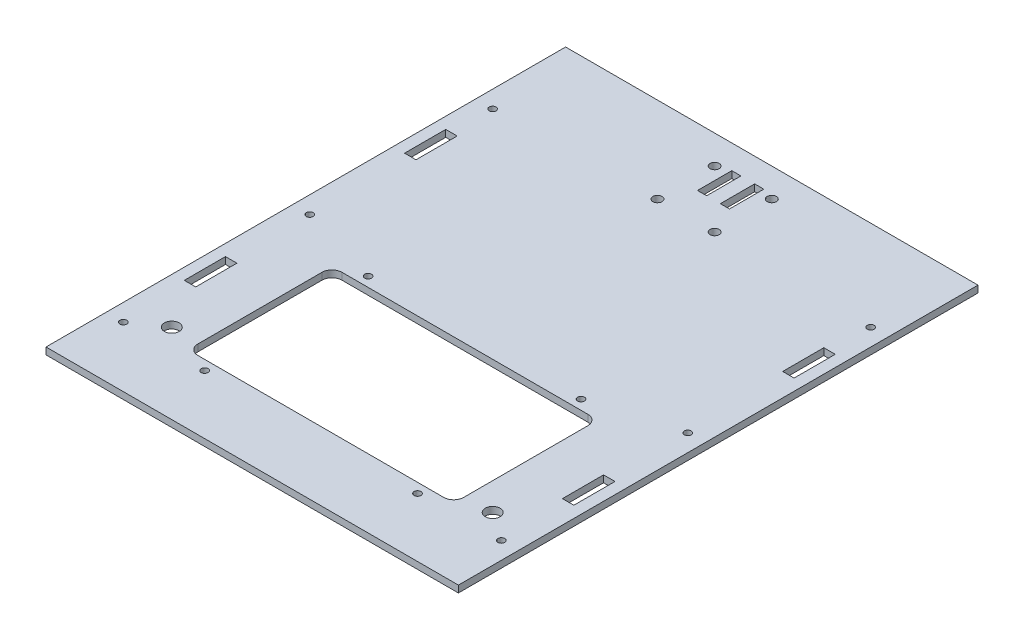
SolidWorks part; units mm, degrees
material "PMMA"
ref_plane "Front Plane" through (0, 0, 0) normal (0, 0, 1) x (1, 0, 0)
ref_plane "Top Plane" through (0, 0, 0) normal (0, 1, 0) x (1, 0, 0)
ref_plane "Right Plane" through (0, 0, 0) normal (1, 0, 0) x (0, 0, -1)
sketch "Schizzo1" plane through (0, 0, 0) normal (0, 1, 0) x (1, 0, 0)
  line L0 (90.17, 113.61) -> (-90.17, -113.61) construction
  line L1 (-90.17, 113.61) -> (90.17, 113.61)
  line L2 (-90.17, 113.61) -> (-90.17, -113.61)
  line L3 (-90.17, -113.61) -> (90.17, -113.61)
  line L4 (90.17, 113.61) -> (90.17, -113.61)
  point P4 (0, 0)
  dimension "D1" = 227.22
  dimension "D2" = 180.34
extrude "Estrusione-Estrusione1" add sketch "Schizzo1" along normal blind 3
sketch "Schizzo3" plane through (0, 0, 0) normal (0, 1, 0) x (1, 0, 0)
  line L0 (0, 113.61) -> (0, -113.61) construction
  line L1 (-58.115, -20.61) -> (58.115, -20.61) construction
  line L2 (-58.115, -20.61) -> (-58.115, -83.61) construction
  line L3 (-58.115, -83.61) -> (58.115, -83.61) construction
  line L4 (58.115, -20.61) -> (58.115, -83.61) construction
  line L5 (90.17, 113.61) -> (-90.17, 113.61) construction
  line L6 (-90.17, -113.61) -> (90.17, -113.61) construction
  line L7 (-53.765, -20.61) -> (53.765, -20.61)
  line L8 (-58.115, -24.96) -> (-58.115, -79.26)
  line L9 (-53.765, -83.61) -> (53.765, -83.61)
  line L10 (58.115, -24.96) -> (58.115, -79.26)
  line L11 (-46.55, -16.36) -> (-46.55, -87.86) construction
  line L12 (58.115, -52.11) -> (-58.115, -52.11) construction
  line L13 (46.55, -16.36) -> (-46.55, -16.36) construction
  line L14 (46.55, -16.36) -> (46.55, -87.86) construction
  line L15 (-46.55, -87.86) -> (46.55, -87.86) construction
  arc A0 (-53.765, -20.61) -> (-58.115, -24.96) centre (-53.765, -24.96) ccw
  arc A1 (-53.765, -83.61) -> (-58.115, -79.26) centre (-53.765, -79.26) cw
  arc A2 (58.115, -79.26) -> (53.765, -83.61) centre (53.765, -79.26) cw
  arc A3 (53.765, -20.61) -> (58.115, -24.96) centre (53.765, -24.96) cw
  circle A4 centre (-46.55, -16.36) radius 1.5
  circle A5 centre (-46.55, -87.86) radius 1.5
  circle A6 centre (46.55, -16.36) radius 1.5
  circle A7 centre (46.55, -87.86) radius 1.5
  point P10 (0, -83.61)
  point P29 (-46.55, -52.11)
  point P32 (0, -16.36)
  dimension "D12" = 3
  dimension "D1" = 116.23
  dimension "D2" = 63
  dimension "D3" = 30
  dimension "D4" = 4.35
  dimension "D5" = 4.35
  dimension "D6" = 4.35
  dimension "D7" = 4.35
  dimension "D8" = 4.35
  dimension "D9" = 4.35
  dimension "D10" = 4.35
  dimension "D11" = 4.35
  dimension "D13" = 71.5
  dimension "D14" = 93.1
sketch "Schizzo2" plane through (0, 0, 0) normal (0, 1, 0) x (1, 0, 0)
  line L0 (90.17, -113.61) -> (90.17, 113.61) construction
  line L1 (85.17, -40.13) -> (80.17, -40.13)
  line L2 (85.17, -40.13) -> (85.17, -58.13)
  line L3 (85.17, -58.13) -> (80.17, -58.13)
  line L4 (80.17, -40.13) -> (80.17, -58.13)
  line L5 (-90.17, -113.61) -> (90.17, -113.61) construction
  line L6 (0, -113.61) -> (0, 113.61) construction
  line L7 (90.17, 113.61) -> (-90.17, 113.61) construction
  line L8 (-85.17, -40.13) -> (-80.17, -40.13)
  line L9 (-85.17, -40.13) -> (-85.17, -58.13)
  line L10 (-85.17, -58.13) -> (-80.17, -58.13)
  line L11 (-80.17, -40.13) -> (-80.17, -58.13)
  line L12 (-82.67, 113.61) -> (-82.67, -113.61) construction
  line L13 (-90.17, -78.61) -> (90.17, -78.61) construction
  line L14 (-85.17, 38.19) -> (-80.17, 38.19)
  line L15 (-85.17, 38.19) -> (-85.17, 56.19)
  line L16 (-85.17, 56.19) -> (-80.17, 56.19)
  line L17 (-80.17, 38.19) -> (-80.17, 56.19)
  line L18 (85.17, 38.19) -> (80.17, 38.19)
  line L19 (80.17, 38.19) -> (80.17, 56.19)
  line L20 (85.17, 56.19) -> (80.17, 56.19)
  line L21 (85.17, 38.19) -> (85.17, 56.19)
  line L22 (7, 103.11) -> (3, 103.11)
  line L23 (-90.17, 113.61) -> (-90.17, -113.61) construction
  line L24 (-7, 103.11) -> (-3, 103.11)
  line L25 (-7, 103.11) -> (-7, 88.11)
  line L26 (-7, 88.11) -> (-3, 88.11)
  line L27 (-3, 103.11) -> (-3, 88.11)
  line L28 (7, 103.11) -> (7, 88.11)
  line L29 (7, 88.11) -> (3, 88.11)
  line L30 (3, 103.11) -> (3, 88.11)
  circle A0 centre (-82.67, -5.81) radius 1.5
  circle A1 centre (-82.67, -87.31) radius 1.5
  circle A2 centre (-82.67, 74.19) radius 1.5
  circle A3 centre (82.67, -87.31) radius 1.5
  circle A4 centre (82.67, -5.81) radius 1.5
  circle A5 centre (82.67, 74.19) radius 1.5
  circle A6 centre (-70.17, -78.61) radius 3.25
  circle A7 centre (70.17, -78.61) radius 3.25
  circle A8 centre (-12.5, 101.11) radius 2
  circle A9 centre (-12.5, 76.11) radius 2
  circle A10 centre (12.5, 76.11) radius 2
  circle A11 centre (12.5, 101.11) radius 2
  point P18 (-82.67, -58.13)
  dimension "D6" = 3
  dimension "D11" = 6.5
  dimension "D13" = 4
  dimension "D2" = 5
  dimension "D4" = 18
  dimension "D3" = 55.48
  dimension "D5" = 57.42
  dimension "D7" = 26.3
  dimension "D8" = 107.8
  dimension "D9" = 187.8
  dimension "D10" = 35
  dimension "D12" = 20
  dimension "D14" = 12.5
  dimension "D15" = 25
  dimension "D16" = 12.5
  dimension "D17" = 12.5
  dimension "D18" = 4
  dimension "D19" = 3
  dimension "D20" = 10.5
  dimension "D21" = 15
extrude "Taglio-Estrusione1" cut sketch "Schizzo2" along direction (0, 1, 0) on the side of the normal through all
extrude "Taglio-Estrusione5" cut sketch "Schizzo3" along direction (0, 1, 0) on the side of the normal through all
equation "\"Thickness5\"= 5"
equation "\"D1@Estrusione-Estrusione1\"=\"Thickness3\""
equation "\"D1@Schizzo2\"=\"Thickness5\""
equation "\"D2@Schizzo2\"=\"Thickness5\""
equation "\"Thickness3\"= 3"
equation "\"D5@Schizzo3\"=\"D4@Schizzo3\""
equation "\"D6@Schizzo3\"=\"D5@Schizzo3\""
equation "\"D7@Schizzo3\"=\"D6@Schizzo3\""
equation "\"D8@Schizzo3\"=\"D7@Schizzo3\""
equation "\"D9@Schizzo3\"=\"D8@Schizzo3\""
equation "\"D10@Schizzo3\"=\"D9@Schizzo3\""
equation "\"D11@Schizzo3\"=\"D10@Schizzo3\""
